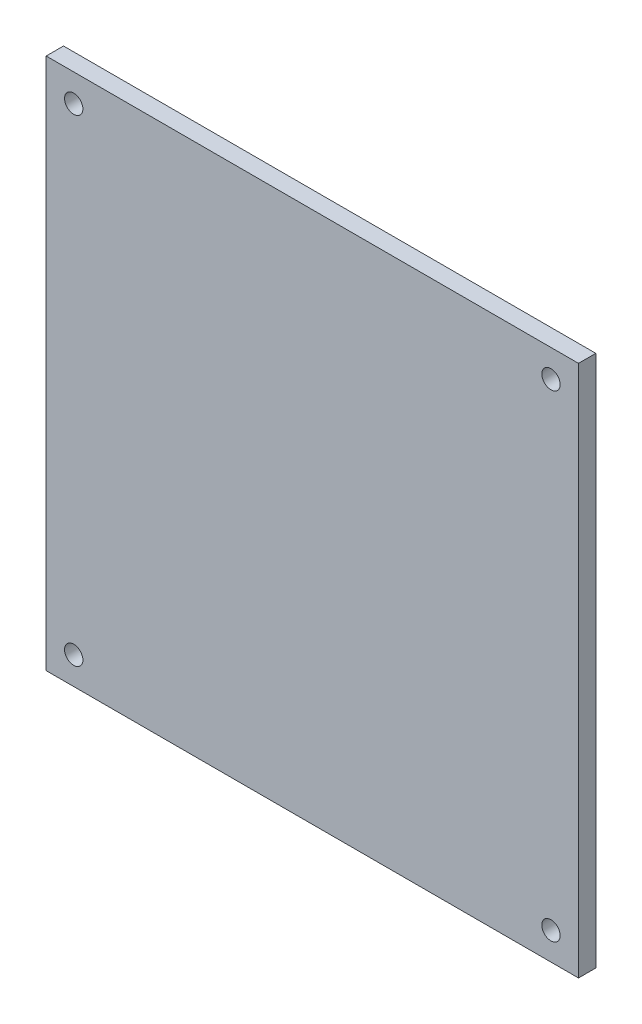
SolidWorks part; units mm, degrees
ref_plane "Front Plane" through (0, 0, 0) normal (0, 0, 1) x (1, 0, 0)
ref_plane "Top Plane" through (0, 0, 0) normal (0, 1, 0) x (1, 0, 0)
ref_plane "Right Plane" through (0, 0, 0) normal (1, 0, 0) x (0, 0, -1)
sketch "Sketch1" plane through (0, 0, 0) normal (0, 0, 1) x (1, 0, 0)
  line L0 (92.075, 184.15) -> (92.075, 0) construction
  line L1 (0, 0) -> (184.15, 0)
  line L2 (0, 0) -> (0, 184.15)
  line L3 (0, 184.15) -> (184.15, 184.15)
  line L4 (184.15, 0) -> (184.15, 184.15)
  line L5 (0, 92.075) -> (184.15, 92.075) construction
  circle A0 centre (9.525, 174.625) radius 3.175
  circle A1 centre (9.525, 9.525) radius 3.175
  circle A2 centre (174.625, 174.625) radius 3.175
  circle A3 centre (174.625, 9.525) radius 3.175
  point P19 (59.4373, 140.8445)
  point P20 (-405.3517, 267.2263)
  dimension "D3" = 6.35
  dimension "D5" = 82.55
  dimension "D1" = 184.15
  dimension "D2" = 184.15
  dimension "D4" = 165.1
  dimension "D6" = 165.1
  dimension "D7" = 82.55
extrude "Boss-Extrude1" add sketch "Sketch1" along normal blind 5.9944
